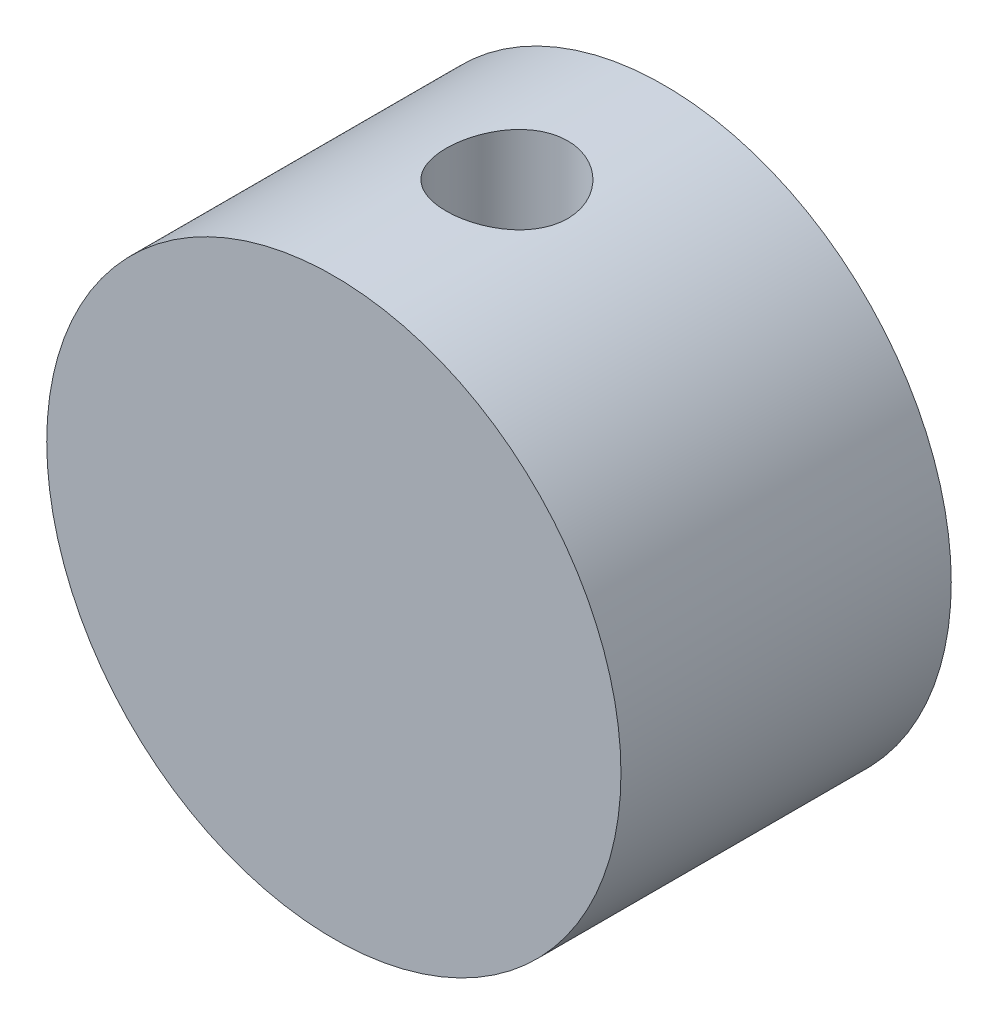
SolidWorks part; units mm, degrees
material "201 Annealed Stainless Steel (SS)"
ref_plane "Front Plane" through (0, 0, 0) normal (0, 0, 1) x (1, 0, 0)
ref_plane "Top Plane" through (0, 0, 0) normal (0, 1, 0) x (1, 0, 0)
ref_plane "Right Plane" through (0, 0, 0) normal (1, 0, 0) x (0, 0, -1)
sketch "Sketch1" plane through (0, 0, 0) normal (0, 0, 1) x (1, 0, 0)
  circle A0 centre (0, 0) radius 16.515
  dimension "D1" = 33.03
extrude "Boss-Extrude1" add sketch "Sketch1" along normal blind 19
sketch "Sketch2" plane through (0, 0, 0) normal (0, 1, 0) x (1, 0, 0)
  circle A0 centre (0, -9.0452) radius 3.5
  dimension "D1" = 7
extrude "Cut-Extrude1" cut sketch "Sketch2" along normal through all
sketch "Sketch3" plane through (0, 0, 0) normal (0, 0, 1) x (1, 0, 0)
  line L0 (0, 0) -> (-17.3205, 10)
  line L1 (0, 0) -> (0, 9.6127) construction
  dimension "D1" = 20
  dimension "60" = 60
ref_plane "Plane1" through (-17.3205, 10, 0) normal (-0.866, 0.5, 0) x (0, 0, 1)
sketch "Sketch4" plane through (-17.3205, 10, 0) normal (-0.866, 0.5, 0) x (0, 0, 1)
  line L0 (0, -173205.0808) -> (0, 173213.4056) construction
  circle A0 centre (9.5, 0) radius 1
  dimension "D2" = 2
  dimension "D1" = 9.5
extrude "Cut-Extrude2" cut sketch "Sketch4" against normal blind 19 contours A0
ref_axis "Axis1" through (0, 0, 19) along (0, 0, -1)
